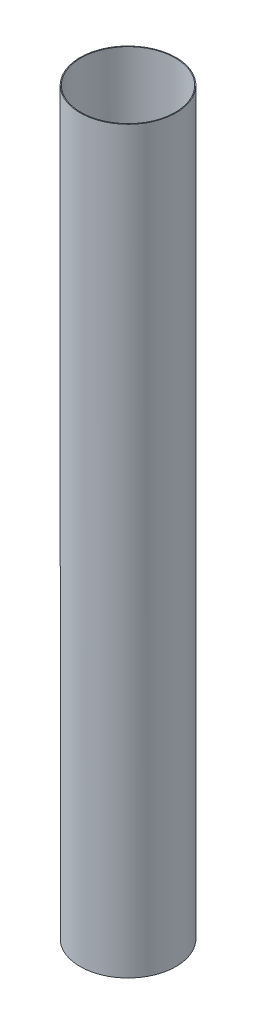
SolidWorks part; units mm, degrees
material "Acrylic (Medium-high impact)"
ref_plane "Front Plane" through (0, 0, 0) normal (0, 0, 1) x (1, 0, 0)
ref_plane "Top Plane" through (0, 0, 0) normal (0, 1, 0) x (1, 0, 0)
ref_plane "Right Plane" through (0, 0, 0) normal (1, 0, 0) x (0, 0, -1)
sketch "Sketch1" plane through (0, 0, 0) normal (0, 1, 0) x (1, 0, 0)
  circle A0 centre (0, 0) radius 30.5
  circle A1 centre (0, 0) radius 30
extrude "Boss-Extrude1" add sketch "Sketch1" along normal up to surface (470 mm away)
